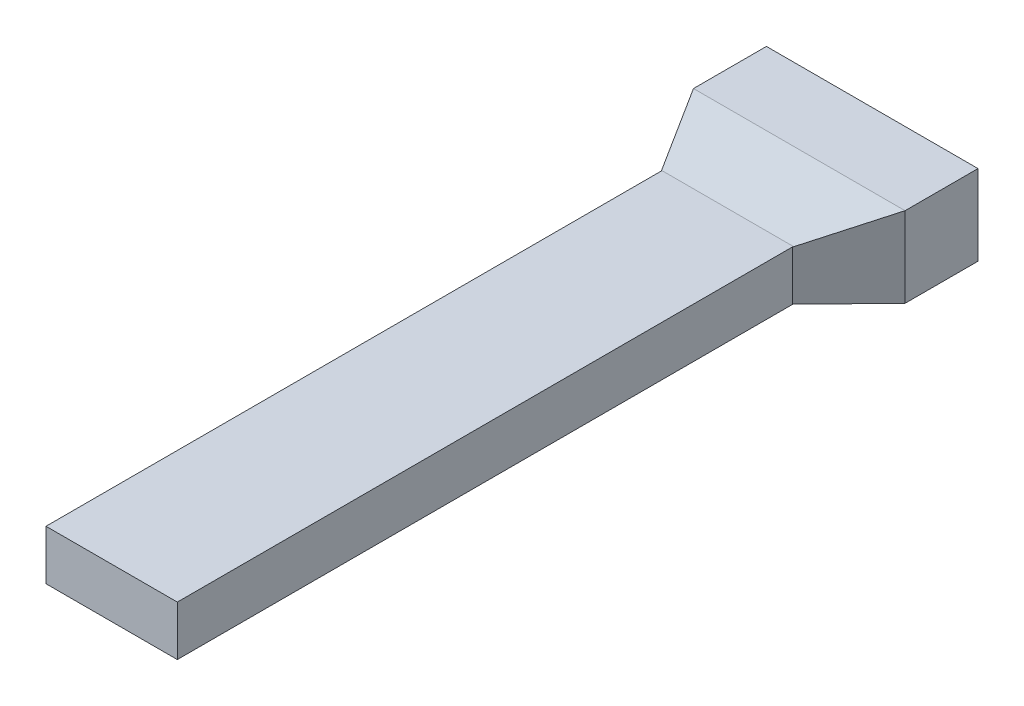
SolidWorks part; units mm, degrees
ref_plane "Alzado" through (0, 0, 0) normal (0, 0, 1) x (1, 0, 0)
ref_plane "Planta" through (0, 0, 0) normal (0, 1, 0) x (1, 0, 0)
ref_plane "Vista lateral" through (0, 0, 0) normal (1, 0, 0) x (0, 0, -1)
sketch "Croquis1" plane through (0, 0, 0) normal (0, 0, 1) x (1, 0, 0)
  line L1 (-22.3085, -1.3317) -> (6.6915, -1.3317)
  line L2 (-22.3085, -1.3317) -> (-22.3085, -12.3317)
  line L3 (-22.3085, -12.3317) -> (6.6915, -12.3317)
  line L4 (6.6915, -1.3317) -> (6.6915, -12.3317)
extrude "Saliente-Extruir1" add sketch "Croquis1" along normal blind 10
sketch "Croquis2" plane through (0, 0, 10) normal (0, 0, 1) x (1, 0, 0)
  line L0 (-22.3085, -1.3317) -> (6.6915, -12.3317)
  line L1 (-22.3085, -12.3317) -> (6.6915, -1.3317)
  line L3 (1.1915, -10.2455) -> (-16.8085, -10.2455)
  line L4 (1.1915, -10.2455) -> (1.1915, -3.4179)
  line L5 (1.1915, -3.4179) -> (-16.8085, -3.4179)
  line L6 (-16.8085, -10.2455) -> (-16.8085, -3.4179)
  line L7 (1.1915, -10.2455) -> (-16.8085, -3.4179) construction
  line L8 (1.1915, -3.4179) -> (-16.8085, -10.2455) construction
  line L9 (-22.3085, -1.3317) -> (6.6915, -1.3317)
  line L10 (-22.3085, -1.3317) -> (-22.3085, -12.3317)
  line L11 (-22.3085, -12.3317) -> (6.6915, -12.3317)
  line L12 (6.6915, -1.3317) -> (6.6915, -12.3317)
  point P8 (-7.8085, -6.8317)
extrude "Saliente-Extruir2" add sketch "Croquis2" along normal blind 94.25 contours L5 L6 L3 L4
sketch "Croquis3" plane through (0, 0, 10) normal (0, 0, 1) x (1, 0, 0)
  line L1 (-22.3085, -1.3317) -> (6.6915, -1.3317)
  line L2 (-22.3085, -1.3317) -> (-22.3085, -12.3317)
  line L3 (-22.3085, -12.3317) -> (6.6915, -12.3317)
  line L4 (6.6915, -1.3317) -> (6.6915, -12.3317)
extrude "Saliente-Extruir5" add sketch "Croquis3" along normal blind 10 separate body
chamfer "Chaflán1" distance 10 angle 12 1 edges at (-7.8085, -12.3317, 20) first distance on face at (-7.8085, -12.3317, 15)
chamfer "Chaflán2" distance 10 angle 12 1 edges at (-7.8085, -1.3317, 20) first distance on face at (-7.8085, -1.3317, 15)
chamfer "Chaflán6" distance 10 angle 29 1 edges at (6.6915, -6.8317, 20) first distance on face at (6.6915, -6.8317, 15)
chamfer "Chaflán7" distance 10 angle 29 1 edges at (-22.3085, -6.8317, 20) first distance on face at (-22.3085, -6.8317, 15)
